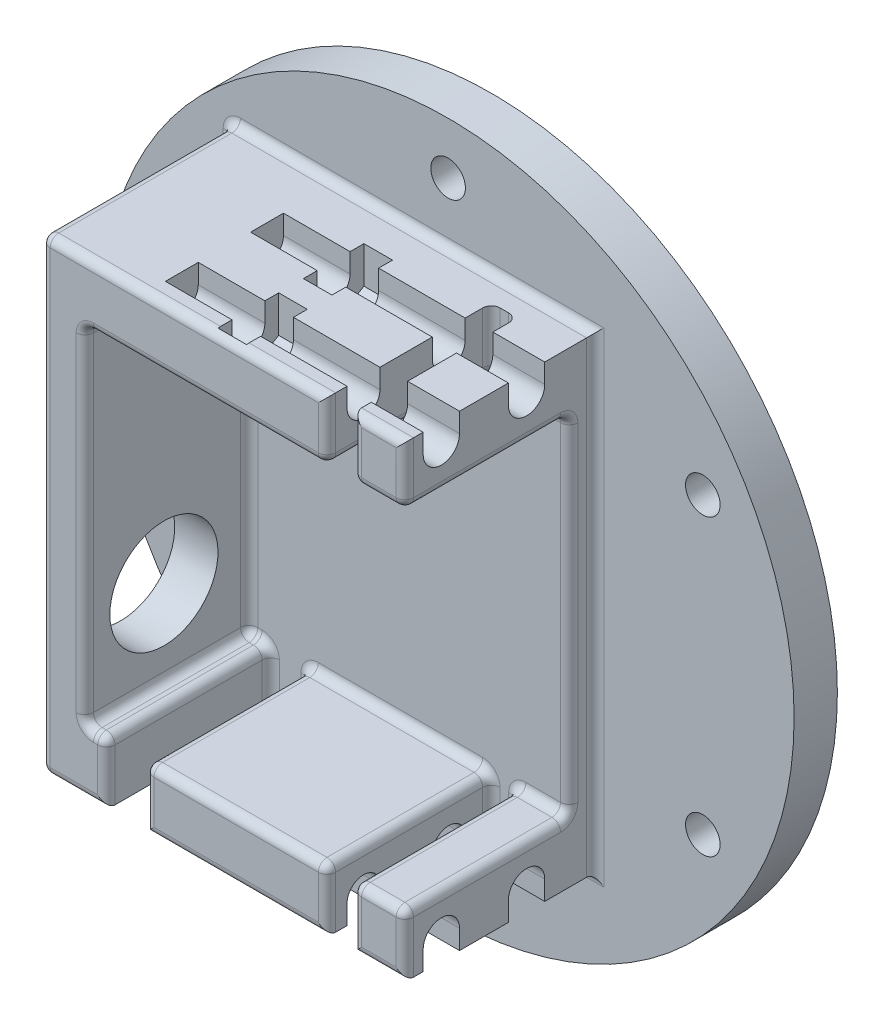
SolidWorks part; units mm, degrees
ref_plane "Plano frontal" through (0, 0, 0) normal (0, 0, 1) x (1, 0, 0)
ref_plane "Plano superior" through (0, 0, 0) normal (0, 1, 0) x (1, 0, 0)
ref_plane "Plano direito" through (0, 0, 0) normal (1, 0, 0) x (0, 0, -1)
sketch "Esboço1" plane through (0, 0, 0) normal (0, 0, 1) x (1, 0, 0)
  circle A0 centre (0, 0) radius 40
  circle A1 centre (0, 34) radius 2
  circle A2 centre (29.4449, 17) radius 2
  circle A3 centre (29.4449, -17) radius 2
  circle A4 centre (0, -34) radius 2
  circle A5 centre (-29.4449, -17) radius 2
  circle A6 centre (-29.4449, 17) radius 2
  point P18 (0, 0)
  dimension "D1" = 80
  dimension "D3" = 4
  dimension "D4" = 34
  dimension "D2" = 6
extrude "Ressalto-extrusão1" add sketch "Esboço1" along normal blind 5
ref_plane "Plano2" through (0, 0, 8) normal (0, 0, 1) x (1, 0, 0)
sketch "Esboço2" plane through (0, 0, 8) normal (0, 0, 1) x (1, 0, 0)
  line L0 (-17.5, 27) -> (-13, 27)
  line L1 (-20, 20) -> (17, 20) construction
  line L2 (-20, 20) -> (-20, -20) construction
  line L3 (-20, -20) -> (20, -20) construction
  line L4 (20, 0) -> (20, -20) construction
  line L5 (-20, 20) -> (20, -20) construction
  line L6 (-20, -20) -> (20, 20) construction
  line L7 (20, 0) -> (-20, 0) construction
  line L8 (-13, 27) -> (8, 27)
  line L10 (-13, 20) -> (8, 20)
  line L11 (8, 27) -> (8, 20)
  line L12 (-13, 27) -> (8, 20) construction
  line L13 (-13, 20) -> (8, 27) construction
  line L15 (-20, 20) -> (-20, -20)
  line L17 (-25, 20) -> (-25, -20)
  line L18 (-20, 20) -> (-17.5, 20)
  line L19 (-25, 20) -> (-25, 27)
  line L20 (-25, 27) -> (-17.5, 27)
  line L22 (8, -27) -> (8, -20)
  line L23 (-13, -27) -> (8, -27)
  line L24 (-13, -27) -> (-13, -20)
  line L25 (-13, -20) -> (8, -20)
  line L26 (-20, -20) -> (-17.5, -20)
  line L27 (-17.5, -20) -> (-17.5, -27)
  line L28 (-25, -27) -> (-17.5, -27)
  line L29 (-25, -20) -> (-25, -27)
  line L30 (-17.5, 20) -> (-13, 20)
  line L31 (17, 20) -> (17, 27)
  line L32 (11, 20) -> (17, 20)
  line L33 (11, 20) -> (11, 27)
  line L34 (11, 27) -> (17, 27)
  line L40 (11, -20) -> (17, -20)
  line L41 (11, -20) -> (11, -27)
  line L42 (11, -27) -> (17, -27)
  line L43 (17, -20) -> (17, -27)
  line L44 (19.5, 20) -> (20, 20) construction
  line L45 (20, 0) -> (20, 20) construction
  line L46 (17, 20) -> (19.5, 20) construction
  point P0 (0, 0)
  point P10 (-2.5, 23.5)
  dimension "D1" = 40
  dimension "D2" = 40
  dimension "D3" = 21
  dimension "D4" = 7
  dimension "D5" = 5
  dimension "D6" = 2.5
  dimension "D7" = 7
  dimension "D8" = 40
  dimension "D9" = 4.5
  dimension "D10" = 3
  dimension "D11" = 6
  dimension "D13" = 7
  dimension "D14" = 7
  dimension "D17" = 6
extrude "Ressalto-extrusão2" add sketch "Esboço2" along normal blind 19
sketch "Esboço3" plane through (17, 0, 0) normal (1, 0, 0) x (0, 0, -1)
  line L0 (0, 0) -> (-27, 0) construction
  line L1 (-27, -20) -> (-27, 20) construction
  line L2 (-24, -24.76) -> (-5, -24.76) construction
  line L3 (-10.83, 27) -> (-15.03, 27)
  line L5 (-27, -20) -> (-8, -20) construction
  line L6 (-24.88, -24.76) -> (-24.88, -27)
  line L7 (-27, -27) -> (-8, -27) construction
  line L8 (-20.68, -24.76) -> (-20.68, -27)
  line L9 (-20.68, -27) -> (-24.88, -27)
  line L10 (-15.03, -24.76) -> (-15.03, -27)
  line L11 (-10.83, -24.76) -> (-10.83, -27)
  line L12 (-10.83, -27) -> (-15.03, -27)
  line L13 (-10.83, 24.76) -> (-10.83, 27)
  line L14 (-15.03, 24.76) -> (-15.03, 27)
  line L15 (-20.68, 27) -> (-24.88, 27)
  line L16 (-20.68, 24.76) -> (-20.68, 27)
  line L17 (-24.88, 24.76) -> (-24.88, 27)
  line L18 (-8, 44) -> (-8, -44) construction
  arc A0 (-20.68, -24.76) -> (-24.88, -24.76) centre (-22.78, -24.76) ccw
  arc A1 (-10.83, -24.76) -> (-15.03, -24.76) centre (-12.93, -24.76) ccw
  arc A2 (-10.83, 24.76) -> (-15.03, 24.76) centre (-12.93, 24.76) cw
  arc A3 (-20.68, 24.76) -> (-24.88, 24.76) centre (-22.78, 24.76) cw
  dimension "D1" = 4.2
  dimension "D2" = 9.85
  dimension "D3" = 4.93
  dimension "D4" = 4.76
extrude "Corte-extrusão1" cut sketch "Esboço3" against normal up to surface (9 mm away) up to face at (8, 23.5, 17.5)
sketch "Esboço4" plane through (8, 0, 0) normal (1, 0, 0) x (0, 0, -1)
  line L1 (-24.68, -24.76) -> (-24.68, -27)
  line L2 (-27, -27) -> (-8, -27) construction
  line L3 (-20.88, -24.76) -> (-20.88, -27)
  line L4 (-20.88, -27) -> (-24.68, -27)
  line L5 (-14.83, -24.76) -> (-14.83, -27)
  line L6 (-11.03, -24.76) -> (-11.03, -27)
  line L7 (-14.83, -27) -> (-11.03, -27)
  line L8 (14.85, 0) -> (-14.85, 0) construction
  line L9 (-14.83, 27) -> (-11.03, 27)
  line L10 (-11.03, 24.76) -> (-11.03, 27)
  line L11 (-14.83, 24.76) -> (-14.83, 27)
  line L12 (-20.88, 27) -> (-24.68, 27)
  line L13 (-20.88, 24.76) -> (-20.88, 27)
  line L14 (-24.68, 24.76) -> (-24.68, 27)
  arc A0 (-20.88, -24.76) -> (-24.68, -24.76) centre (-22.78, -24.76) ccw
  arc A1 (-11.03, -24.76) -> (-14.83, -24.76) centre (-12.93, -24.76) ccw
  arc A4 (-11.03, 24.76) -> (-14.83, 24.76) centre (-12.93, 24.76) cw
  arc A5 (-20.88, 24.76) -> (-24.68, 24.76) centre (-22.78, 24.76) cw
  dimension "D1" = 3.8
sketch "Esboço7" plane through (0, 0, 5) normal (0, 0, 1) x (1, 0, 0)
  line L1 (-25, 27) -> (17, 27)
  line L2 (-25, 27) -> (-25, -27)
  line L3 (-25, -27) -> (17, -27)
  line L4 (17, 27) -> (17, -27)
extrude "Ressalto-extrusão4" add sketch "Esboço7" along normal blind 3
extrude "Corte-extrusão2" cut sketch "Esboço4" against normal up to surface (21 mm away) up to face at (-13, -23.5, 17.5)
ref_plane "Plano1" through (-2, 0, 0) normal (1, 0, 0) x (0, 0, -1)
sketch "Esboço5" plane through (-2, 0, 0) normal (1, 0, 0) x (0, 0, -1)
  line L0 (-20.88, 24.76) -> (-20.88, 27) construction
  line L1 (-19.28, 22.7393) -> (-19.28, 26.7807)
  line L4 (-26.28, 26.7807) -> (-26.28, 22.7393)
  line L5 (-26.28, 22.7393) -> (-22.78, 20.7185)
  line L6 (-22.78, 20.7185) -> (-19.28, 22.7393)
  line L7 (-26.28, 26.7807) -> (-26.28, 27)
  line L8 (-27, 27) -> (-24.88, 27) construction
  line L9 (-26.28, 27) -> (-19.28, 27)
  line L10 (-20.68, 27) -> (-15.03, 27) construction
  line L11 (-19.28, 27) -> (-19.28, 26.7807)
  line L12 (-17.855, 27) -> (-17.855, -27) construction
  line L13 (-25.9002, 27) -> (-26.132, 26.8662) [skipped]
  line L14 (-19.28, 26.7807) -> (-19.6598, 27) [skipped]
  line L15 (-20.68, -27) -> (-15.03, -27) construction
  line L16 (-16.43, 27) -> (-16.43, 26.7807)
  line L17 (-9.43, 27) -> (-16.43, 27)
  line L18 (-9.43, 26.7807) -> (-9.43, 27)
  line L19 (-12.93, 20.7185) -> (-16.43, 22.7393)
  line L20 (-9.43, 22.7393) -> (-12.93, 20.7185)
  line L21 (-9.43, 26.7807) -> (-9.43, 22.7393)
  line L22 (-16.43, 22.7393) -> (-16.43, 26.7807)
  line L23 (14.85, 0) -> (-14.85, 0) construction
  line L24 (-16.43, -22.7393) -> (-16.43, -26.7807)
  line L25 (-9.43, -26.7807) -> (-9.43, -22.7393)
  line L26 (-9.43, -22.7393) -> (-12.93, -20.7185)
  line L27 (-12.93, -20.7185) -> (-16.43, -22.7393)
  line L28 (-9.43, -26.7807) -> (-9.43, -27)
  line L29 (-9.43, -27) -> (-16.43, -27)
  line L30 (-16.43, -27) -> (-16.43, -26.7807)
  line L31 (-19.28, -27) -> (-19.28, -26.7807)
  line L32 (-26.28, -27) -> (-19.28, -27)
  line L33 (-26.28, -26.7807) -> (-26.28, -27)
  line L34 (-22.78, -20.7185) -> (-19.28, -22.7393)
  line L35 (-26.28, -22.7393) -> (-22.78, -20.7185)
  line L36 (-26.28, -26.7807) -> (-26.28, -22.7393)
  line L37 (-19.28, -22.7393) -> (-19.28, -26.7807)
  arc A0 (-25.4693, 27) -> (-20.0907, 27) centre (-22.78, 24.76) ccw construction
  arc A1 (-10.2407, 27) -> (-15.6193, 27) centre (-12.93, 24.76) cw construction
  arc A2 (-10.2407, -27) -> (-15.6193, -27) centre (-12.93, -24.76) ccw construction
  arc A3 (-25.4693, -27) -> (-20.0907, -27) centre (-22.78, -24.76) cw construction
  dimension "D1" = 7
extrude "Corte-extrusão3" cut sketch "Esboço5" against normal blind 3.3
fillet "Filete1" radius 1 23 edges at (17, 20, 17.5) (11, -23.5, 8) (8, -23.5, 8) (-13, -23.5, 8) (-17.5, -23.5, 8) (11, 23.5, 8) (8, 23.5, 8) (17, 0, 8) (11, -20, 17.5) (8, -20, 17.5) (-13, -20, 17.5) (-17.5, -20, 17.5) (11, 20, 17.5) (8, 20, 17.5) (17, -20, 17.5) (-20, -20, 17.5) (-20, 20, 17.5) (-20, 0, 8) (14, -20, 8) (-2.5, -20, 8) (-18.75, -20, 8) (-6, 20, 8) (14, 20, 8)
fillet "Filete2" radius 1 36 edges at (17, -24, 27) (16.7071, -20.2929, 27) (11, -24, 27) (11.2929, -20.2929, 27) (11, 24, 27) (11.2929, 20.2929, 27) (17, 24, 27) (16.7071, 20.2929, 27) (8, -24, 27) (7.7071, -20.2929, 27) (-13, -24, 27) (-12.7071, -20.2929, 27) (-17.5, -24, 27) (-17.7929, -20.2929, 27) (-18.75, -20, 27) (-19.7071, -19.7071, 27) (8, 24, 27) (7.7071, 20.2929, 27) (-6, 20, 27) (-19.7071, 19.7071, 27) (14, -20, 27) (14, 20, 27) (-2.5, -20, 27) (-20, 0, 27) (14, 27, 27) (14, -27, 27) (-2.5, -27, 27) (-8.5, 27, 27) (-25, 0, 27) (-21.25, -27, 27) (-25, -27, 16) (-25, 27, 16) (-25, 0, 5) (-4, 27, 5) (-4, -27, 5) (17, 0, 5)
sketch "Esboço8" plane through (-25, 0, 0) normal (-1, 0, 0) x (0, 0, 1)
  line L0 (6, -26) -> (26, -26) construction
  line L1 (6, 26) -> (6, -26) construction
  circle A0 centre (17.85, -10.15) radius 6.25
  dimension "D1" = 12.5
  dimension "D2" = 15.85
  dimension "D3" = 11.85
extrude "Corte-extrusão4" cut sketch "Esboço8" against normal up to surface (5 mm away) up to face at (-20, 0, 17.5)
